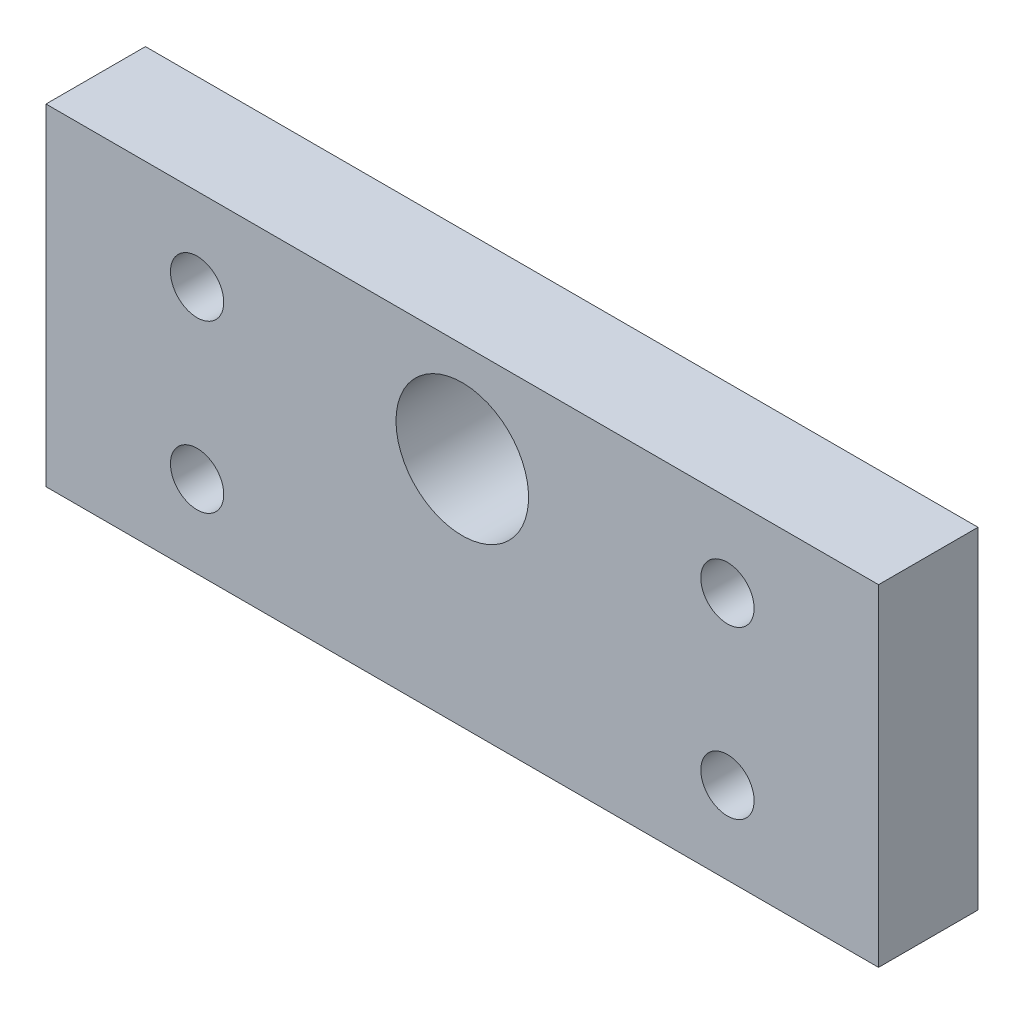
SolidWorks part; units mm, degrees
material "6061-T6 (SS)"
ref_plane "Front Plane" through (0, 0, 0) normal (0, 0, 1) x (1, 0, 0)
ref_plane "Top Plane" through (0, 0, 0) normal (0, 1, 0) x (1, 0, 0)
ref_plane "Right Plane" through (0, 0, 0) normal (1, 0, 0) x (0, 0, -1)
sketch "Sketch1" plane through (0, 0, 0) normal (0, 0, 1) x (1, 0, 0)
  line L2 (39.8731, 0) -> (-39.8731, 0)
  line L3 (39.8731, 0) -> (39.8731, 31.75)
  line L4 (39.8731, 31.75) -> (-39.8731, 31.75)
  line L6 (-39.8731, 0) -> (-39.8731, 31.75)
  circle A0 centre (0, 22.225) radius 6.35
  point P6 (0, 0)
  line B0 (63.5, 0) -> (63.5, 15.875)
  line B1 (63.5, 15.875) -> (36.5092, 15.875)
  line B2 (36.5092, 15.875) -> (47.625, 31.75)
  line B3 (47.625, 31.75) -> (16.0563, 31.75)
  line B4 (-16.0563, 31.75) -> (-16.0563, 12.7)
  line B5 (16.0563, 12.7) -> (16.0563, 31.75)
  line B6 (-63.5, 47.625) -> (63.5, 47.625)
  line B7 (63.5, 47.625) -> (63.5, 15.875)
  line B8 (0, 47.625) -> (0, 0) construction
  line B9 (-36.5092, 15.875) -> (36.5092, 15.875) construction
  line B10 (-28.702, 36.957) -> (28.702, 36.957) construction
  line B11 (-25.4, 7.874) -> (25.4, 7.874) construction
  line B12 (-25.4, 7.874) -> (-25.4, 23.8125) construction
  line B13 (25.4, 7.874) -> (25.4, 23.8125) construction
  line B14 (-52.832, 23.8125) -> (52.832, 23.8125) construction
  circle B15 centre (0, 22.225) radius 18.669 construction
  dimension "D1" = 12.7
sketch_block_instance "dovetail pair-1"
sketch_block "dovetail pair" parameters "D8"=37.338, "D1"=55, "D2"=127, "D3"=6.35, "D4"=15.875, "D5"=31.75, "D6"=95.25, "D7"=19.05, "D9"=55, "D10"=31.75, "D11"=50.8, "D12"=23.876, "D13"=7.874, "D14"=10.668, "D15"=34.798, "D16"=21.082, "D17"=7.9375
extrude "Boss-Extrude1" add sketch "Sketch1" along normal blind 9.525
hole_wizard "CBORE for #10 Socket Head Cap Screw1" positions "Sketch2" profile "Sketch3" counterbore size "#10" standard "ANSI Inch" end condition up to next
sketch "Sketch2" plane through (0, 0, 0) normal (0, 0, 1) x (1, 0, 0)
  point P27 (25.4, 23.8125)
  point P29 (-25.4, 23.8125)
  point P31 (-25.4, 7.874)
  point P33 (25.4, 7.874)
sketch "Sketch3" plane through (25.4, 23.8125, 0) normal (1, 0, 0) x (0, 1, 0)
  line L0 (0, 0) -> (0, 9.525)
  line L1 (0, 9.525) -> (2.5527, 9.525)
  line L3 (2.5527, 9.525) -> (2.5527, 4.826)
  line L4 (4.7625, 4.826) -> (2.5527, 4.826)
  line L5 (4.7625, 4.826) -> (4.7625, 0.635)
  line L6 (4.7625, 0.635) -> (5.3975, 0)
  line L7 (5.3975, 0) -> (0, 0)
  line L8 (-4.7625, 0.635) -> (-5.3975, 0) construction
  line L11 (0, -6.35) -> (0, 107.95) construction
  dimension "Thru Hole Dia." = 5.1054
  dimension "Thru Hole Depth" = 9.525
  dimension "C'Bore Dia." = 9.525
  dimension "C'Bore Depth" = 4.826
  dimension "Near C'Sink Dia." = 10.795
  dimension "Near C'Sink Angle" = 90
ref_plane "center plane" through (0, 0, 0) normal (1, 0, 0) x (0, 0, -1)
equation "\"dovetail-angle\"= 55"
equation "\"dovetail-stock-width\"= 5"
equation "\"dovetail-stock-height\"= 1.25"
equation "\"dovetail-depth\"= 0.5 * \"dovetail-stock-height\""
equation "\"dovetail-throat-width\"= \"dovetail-stock-width\" - (2 * \"dovetail-depth\")"
equation "\"delta-x\"= 6"
equation "\"delta-y\"= 3"
equation "\"gib-thickness\"= 0.25"
equation "\"x-slide-length\"= \"dovetail-stock-width\" + \"delta-x\""
equation "\"y-slide-length\"= \"dovetail-stock-width\" + \"delta-y\""
equation "\"dog-point-diam\"= .149"
equation "\"dog-point-length\"= .067"
equation "\"dovetail-double-height\"= 2 * \"dovetail-depth\" + 0.5"
equation "\"acme-major-diam\"= .5"
equation "\"acme-pitch-diam\"= 0.45"
equation "\"acme-minor-diam\"= 0.4"
equation "\"acme-nut-od\"= 1.47"
equation "\"acme-nut-length\"= 1"
equation "\"acme-nut-trim-height\"= .75"
equation "\"screw-bearing-od\"= 0.5"
equation "\"screw-bearing-length\"= .375"
equation "\"screw-bearing-id\"= .375"
equation "\"end-plate-thickness\"= \"screw-bearing-length\""
equation "\"screw-add-length\"= 2 * \"end-plate-thickness\" + 1 + 0.5"
equation "\"x-screw-length\"= \"x-slide-length\" + \"screw-add-length\""
equation "\"y-screw-length\"= \"y-slide-length\" + \"screw-add-length\""
equation "\"acme-nut-mount-hole-space-horz\"= 0.95"
equation "\"acme-nut-mount-hole-space-vert\"= 0.5 * \"acme-nut-length\""
equation "\"vise-hole-center-dist\"= 6.75"
equation "\"wiper_plate_clearance\"= .03"
equation "\"D1@Boss-Extrude1\"=\"screw-bearing-length\""
equation "\"D2@dovetail pair\"=\"dovetail-stock-width\""
equation "\"D1@dovetail pair\"=\"dovetail-angle\""
equation "\"D3@dovetail pair\"=\"gib-thickness\""
equation "\"D4@dovetail pair\"=\"dovetail-depth\""
equation "\"D5@dovetail pair\"=\"dovetail-stock-height\""
equation "\"D6@dovetail pair\"=\"dovetail-throat-width\""
equation "\"D10@dovetail pair\"=\"dovetail-stock-height\""
equation "\"D7@dovetail pair\"=\"acme-nut-trim-height\""
equation "\"D8@dovetail pair\"=\"acme-nut-od\""
equation "\"D9@dovetail pair\"=\"dovetail-angle\""
equation "\"D17@dovetail pair\"=\"dovetail-depth\"/2"
equation "\"D1@Sketch1\"=\"screw-bearing-od\""
